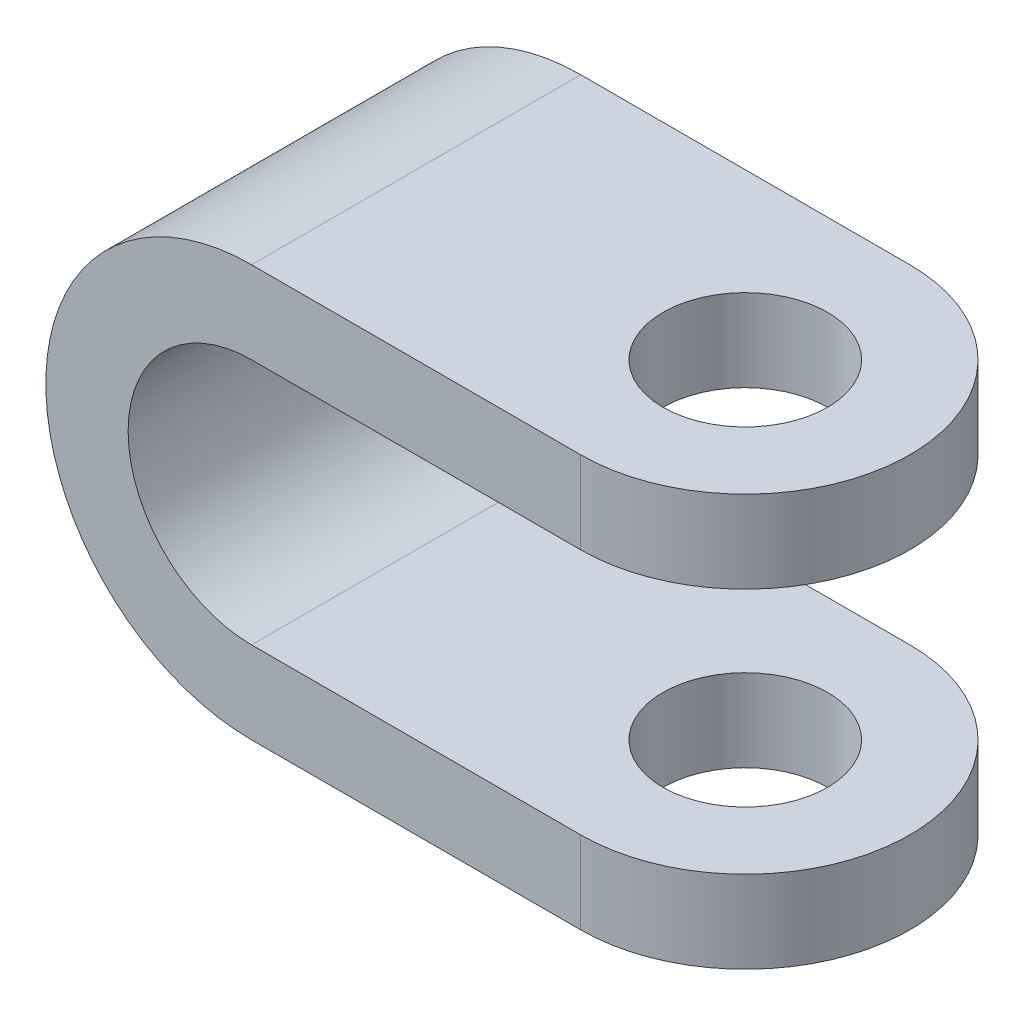
SolidWorks part; units mm, degrees
ref_plane "Front" through (0, 0, 0) normal (0, 0, 1) x (1, 0, 0)
ref_plane "Top" through (0, 0, 0) normal (0, 1, 0) x (1, 0, 0)
ref_plane "Right" through (0, 0, 0) normal (1, 0, 0) x (0, 0, -1)
other "Configuration Table"
sketch "Sketch1" plane through (0, 0, 0) normal (0, 0, 1) x (1, 0, 0)
  line L0 (0, -15) -> (-60, -15)
  line L1 (-60, -65) -> (0, -65)
  arc A0 (-60, -15) -> (-60, -65) centre (-60, -40) ccw
  dimension "D3" = 25
  dimension "D1" = 15
  dimension "D2" = 60
extrude "Extrude-Thin1" add sketch "Sketch1" along normal blind 90 thin thin type one direction reverse wall 10
sketch "Sketch2" plane through (0, 0, 0) normal (0, 1, 0) x (1, 0, 0)
  line L0 (-85, -25) -> (-85, -65)
  line L1 (-85, 0) -> (-85, -90) construction
  line L2 (-85, -65) -> (-20, -65)
  line L3 (-20, -25) -> (-85, -25)
  line L4 (0, -90) -> (0, 0) construction
  arc A0 (-20, -65) -> (-20, -25) centre (-20, -45) ccw
  circle A1 centre (-20, -45) radius 10
  dimension "D2" = 25
  dimension "D3" = 20
  dimension "D1" = 40
extrude "Boss-Extrude1" add sketch "Sketch2" against normal blind 90 separate body
combine bodies "Соединить1" operation type common bodies to combine 101 102
